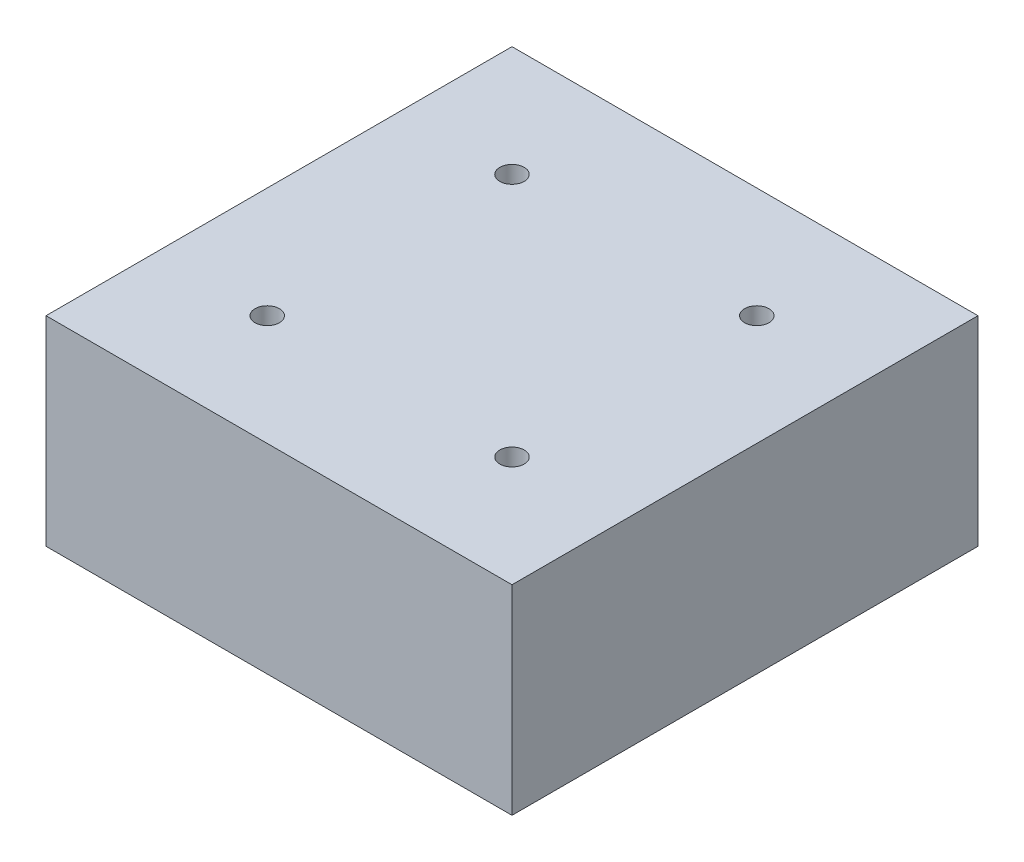
SolidWorks part; units mm, degrees
ref_plane "前视基准面" through (0, 0, 0) normal (0, 0, 1) x (1, 0, 0)
ref_plane "上视基准面" through (0, 0, 0) normal (0, 1, 0) x (1, 0, 0)
ref_plane "右视基准面" through (0, 0, 0) normal (1, 0, 0) x (0, 0, -1)
other "Configuration Table"
sketch "01_Housing_Profile" plane through (0, 0, 0) normal (0, 1, 0) x (1, 0, 0)
  line L1 (-105, -105) -> (105, -105)
  line L2 (-105, -105) -> (-105, 105)
  line L3 (-105, 105) -> (105, 105)
  line L4 (105, -105) -> (105, 105)
  line L5 (-105, -105) -> (105, 105) construction
  line L6 (-105, 105) -> (105, -105) construction
  circle A0 centre (55.1543, 55.1543) radius 5.5
  circle A1 centre (-55.1543, 55.1543) radius 5.5
  circle A2 centre (-55.1543, -55.1543) radius 5.5
  circle A3 centre (55.1543, -55.1543) radius 5.5
  point P0 (0, 0)
extrude "01_Housing_Block" add sketch "01_Housing_Profile" along normal blind 90
sketch "02_Face_Boss_Profile" plane through (0, 0, 0) normal (0, 1, 0) x (1, 0, 0)
  circle A0 centre (0, 0) radius 72.5
extrude "02_Face_Locating_Boss" add sketch "02_Face_Boss_Profile" along normal blind 90
